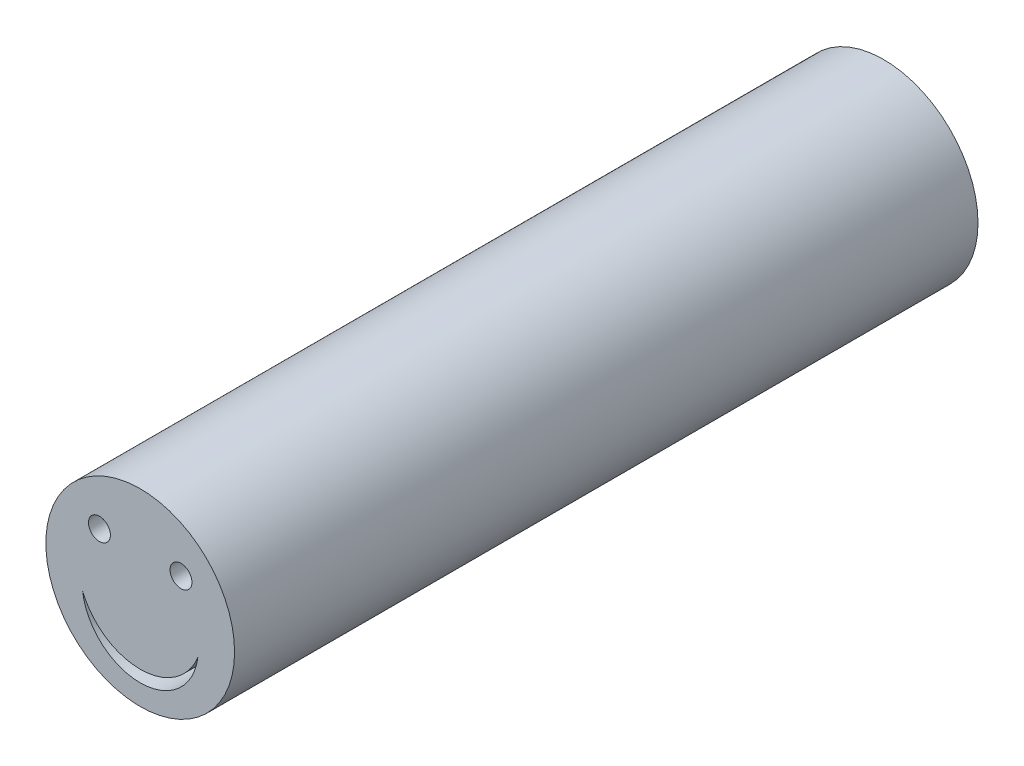
SolidWorks part; units mm, degrees
material "6061-T6 (SS)"
ref_plane "Front Plane" through (0, 0, 0) normal (0, 0, 1) x (1, 0, 0)
ref_plane "Top Plane" through (0, 0, 0) normal (0, 1, 0) x (1, 0, 0)
ref_plane "Right Plane" through (0, 0, 0) normal (1, 0, 0) x (0, 0, -1)
sketch "Sketch1" plane through (0, 0, 0) normal (0, 0, 1) x (1, 0, 0)
  circle A0 centre (0, 0) radius 35.5406
  dimension "D1" = 71.0812
extrude "Boss-Extrude1" add sketch "Sketch1" along normal mid plane 280
sketch "Sketch2" plane through (0, 0, -140) normal (0, 0, -1) x (-1, 0, 0)
  line L0 (-35.5406, 0) -> (35.5406, 0) construction
  circle A0 centre (0, 0) radius 35.5406 construction
  point P7 (0, 0)
ref_axis "mating" through (102.9859, 0, -140) along (-1, 0, 0)
sketch "Sketch3" plane through (0, 0, 140) normal (0, 0, 1) x (1, 0, 0)
  line L0 (0, -35.5406) -> (0, 35.5406) construction
  circle A0 centre (-15.3639, 14.7434) radius 4.1318
  circle A2 centre (0, 0) radius 35.5406 construction
  circle A3 centre (15.3639, 14.7434) radius 4.1318
  arc A4 (-21.7187, -8.5923) -> (21.7187, -8.5923) centre (0, 0) ccw
  arc A5 (-21.7187, -8.5923) -> (21.7187, -8.5923) centre (0, -5.8999) ccw
  point P12 (-21.7187, -8.5923)
  point P13 (-15.3639, 14.7434)
extrude "Cut-Extrude1" cut sketch "Sketch3" against normal through all both and the other way through all
